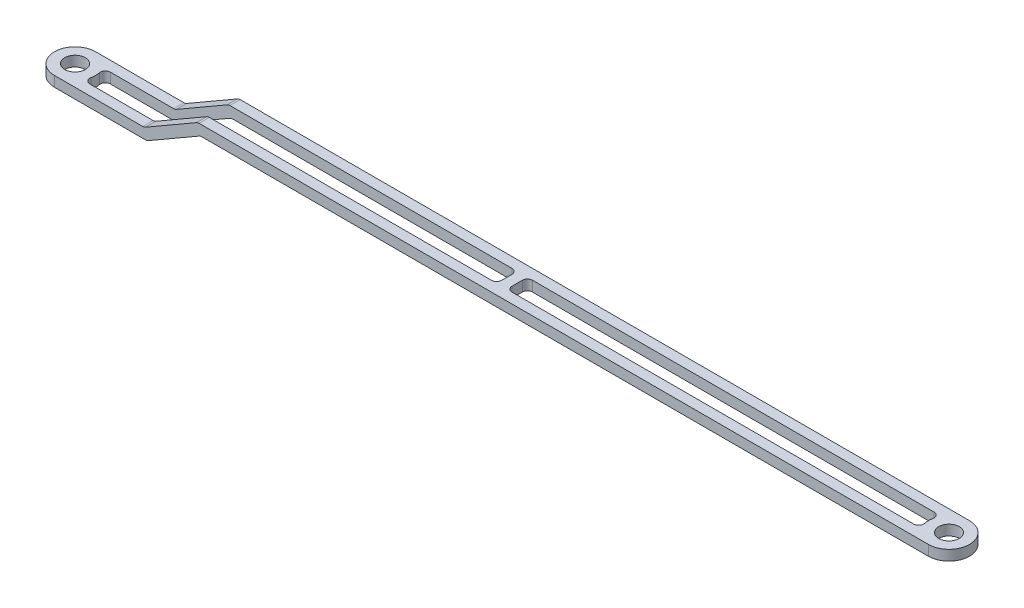
SolidWorks part; units mm, degrees
ref_plane "Front Plane" through (0, 0, 0) normal (0, 0, 1) x (1, 0, 0)
ref_plane "Top Plane" through (0, 0, 0) normal (0, 1, 0) x (1, 0, 0)
ref_plane "Right Plane" through (0, 0, 0) normal (1, 0, 0) x (0, 0, -1)
sketch "Sketch1" plane through (0, 0, 0) normal (0, 1, 0) x (1, 0, 0)
  line L0 (0, 0) -> (170, 0) construction
  line L1 (0, 4) -> (170, 4)
  line L2 (170, 2) -> (0, 2)
  line L3 (0, -2) -> (170, -2)
  line L4 (170, -4) -> (0, -4)
  line L5 (84, 2) -> (84, -2)
  line L6 (86, 2) -> (86, -2)
  line L7 (85, 2) -> (85, -2) construction
  circle A0 centre (0, 0) radius 2
  circle A1 centre (170, 0) radius 2
  circle A2 centre (170, 0) radius 4
  circle A3 centre (0, 0) radius 4
  dimension "D1" = 4
  dimension "D2" = 2
  dimension "D3" = 4
  dimension "D4" = 2
  dimension "D5" = 1
  dimension "D6" = 2
  dimension "D7" = 170
extrude "Boss-Extrude1" add sketch "Sketch1" along normal blind 8 contours A3 L3 A0 L2 | L3 A3 L2 A0 | A3 L2 A2 L1 | A3 L4 A2 L3 | L6 L2 L5 L3 | A2 L2 A1 L3 | A2 | A1 region at (1.9453, 0, -3.3693) region at (85, 0, -3.0054) region at (172.7511, 0, -2.7511) region at (85, 0, 3.0054) region at (2.66, 0, 0) region at (85, 0, 0)
sketch "Sketch2" plane through (0, 0, 4) normal (0, 0, 1) x (1, 0, 0)
  line L0 (-4, 6) -> (174, 6)
  line L1 (-4, 8) -> (174, 8)
  line L2 (-4, 8) -> (-4, 0)
  line L3 (-4, 0) -> (174, 0)
  line L4 (174, 8) -> (174, 0)
  line L5 (174, 2) -> (-4, 2)
  line L6 (16, 0) -> (29.8564, 8) construction
  line L7 (14, 0) -> (27.8564, 8)
  line L8 (18, 0) -> (31.8564, 8)
  line M5 (0, 0) -> (170, 0)
  line M6 (170, 0) -> (170, 8)
  line M8 (0, 8) -> (0, 0)
  dimension "D1" = 2
  dimension "D2" = 2
  dimension "D3" = 30
  dimension "D4" = 20
  dimension "D5" = 1
  dimension "D6" = 2
extrude "Cut-Extrude1" cut sketch "Sketch2" against normal blind 8 contours L5 L7 L0 M8 | L5 L0 L2 M8 | L1 L2 L0 M8 | L0 L7 L1 M8 | L8 L5 M5 M6 | L8 L5 L0 M6 | L5 L4 L0 M6 | L4 L5 L3 M6 region at (-2, 7, 4) region at (-2, 4, 4) region at (13.0813, 7.0221, 4) region at (10.5597, 4.1103, 4) region at (97.4503, 3.9841, 4) region at (172, 4, 4) region at (94.8627, 0.9962, 4) region at (172, 1, 4)
fillet "Fillet1" radius 1 16 edges at (166.5359, 7, -2) (166.5359, 7, 2) (86, 7, 2) (84, 7, 2) (86, 7, -2) (84, 7, -2) (28.3923, 6, -3) (27.8564, 8, -3) (28.3923, 6, 3) (27.8564, 8, 3) (18, 0, -3) (18, 0, 3) (17.4641, 2, 3) (17.4641, 2, -3) (3.4641, 1, 2) (3.4641, 1, -2)
